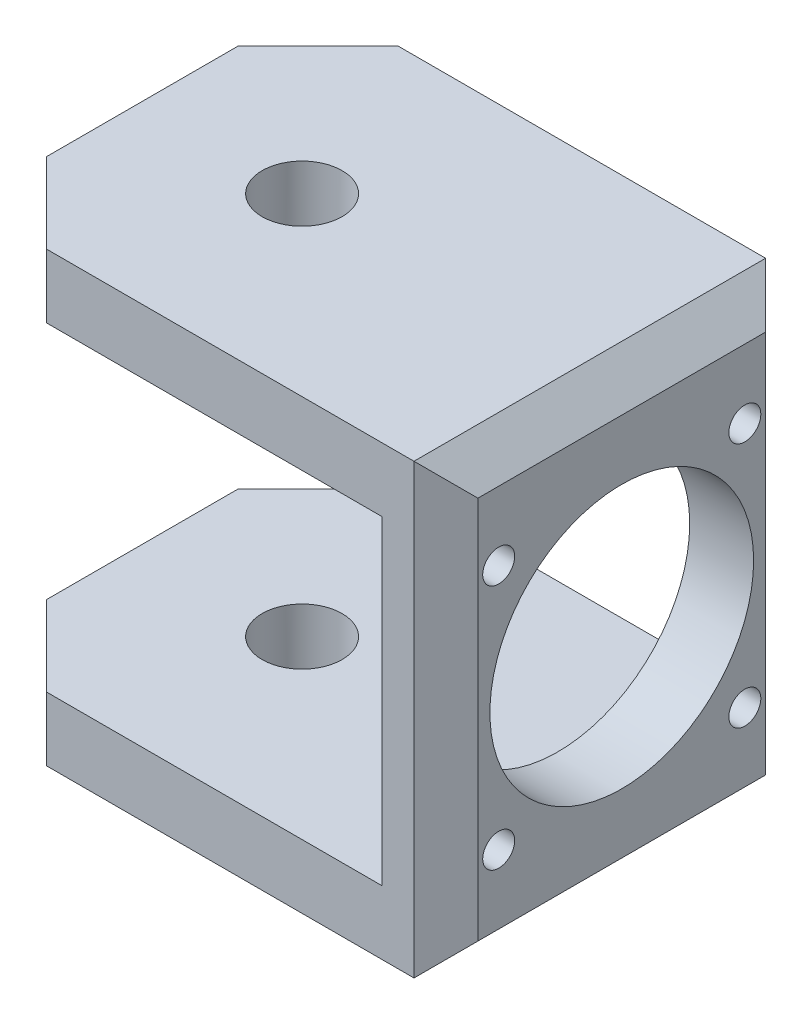
SolidWorks part; units mm, degrees
material "PLA Generic"
ref_plane "Front Plane" through (0, 0, 0) normal (0, 0, 1) x (1, 0, 0)
ref_plane "Top Plane" through (0, 0, 0) normal (0, 1, 0) x (1, 0, 0)
ref_plane "Right Plane" through (0, 0, 0) normal (1, 0, 0) x (0, 0, -1)
sketch "Sketch1" plane through (0, 0, 0) normal (0, 1, 0) x (1, 0, 0)
  line L1 (-15, -11) -> (15, -11)
  line L2 (-15, -11) -> (-15, 11)
  line L3 (-15, 11) -> (15, 11)
  line L4 (15, -11) -> (15, 11)
  line L5 (-15, -11) -> (15, 11) construction
  line L6 (-15, 11) -> (15, -11) construction
  point P0 (0, 0)
  dimension "D1" = 22
  dimension "D2" = 30
extrude "Boss-Extrude1" add sketch "Sketch1" along normal blind 4
sketch "Sketch2" plane through (0, 4, 0) normal (0, 1, 0) x (1, 0, 0)
  line L0 (-15, -11) -> (15, -11) construction
  line L1 (15, 11) -> (11, 11)
  line L2 (15, 11) -> (15, -11)
  line L3 (15, -11) -> (11, -11)
  line L4 (11, 11) -> (11, -11)
  dimension "D1" = 4
extrude "Boss-Extrude2" add sketch "Sketch2" along normal blind 20
sketch "Sketch3" plane through (0, 24, 0) normal (0, 1, 0) x (1, 0, 0)
  line L1 (15, 11) -> (-15, 11)
  line L2 (15, 11) -> (15, -11)
  line L3 (15, -11) -> (-15, -11)
  line L4 (-15, 11) -> (-15, -11)
extrude "Boss-Extrude3" add sketch "Sketch3" along normal blind 4
chamfer "Chamfer1" distance 5 angle 45 4 edges at (-15, 2, 11) (-15, 2, -11) (-15, 26, -11) (-15, 26, 11)
sketch "Sketch4" plane through (15, 0, 0) normal (1, 0, 0) x (0, 0, -1)
  circle A0 centre (0, 14) radius 8.25
  dimension "D1" = 16.5
extrude "Cut-Extrude1" cut sketch "Sketch4" against normal through all
ref_axis "Axis1" through (11, 14, 0) along (1, 0, 0)
sketch "Sketch5" plane through (15, 0, 0) normal (1, 0, 0) x (0, 0, -1)
  line L0 (0, 6.3) -> (-7.7, 6.3) construction
  line L1 (-7.7, 6.3) -> (0, 14) construction
  line L2 (0, 14) -> (0, 6.3) construction
  circle A0 centre (-7.7, 6.3) radius 1
  circle A1 centre (-7.7, 21.7) radius 1
  circle A2 centre (7.7, 21.7) radius 1
  circle A3 centre (7.7, 6.3) radius 1
  point P15 (0, 14)
  dimension "D3" = 2
  dimension "D1" = 45
  dimension "D2" = 7.7
  dimension "D4" = 4
extrude "Cut-Extrude2" cut sketch "Sketch5" against normal through all
chamfer "Chamfer2" distance 2 angle 45 4 edges at (15, 14, -11) (15, 0, 0) (15, 14, 11) (15, 28, 0)
sketch "Sketch6" plane through (0, 28, 0) normal (0, 1, 0) x (1, 0, 0)
  line L0 (11.1707, 0) -> (-17.3457, 0) construction
  line L1 (11, 0) -> (15, 0) construction
  line L2 (-15, 6) -> (-15, -6) construction
  circle A0 centre (-5, 0) radius 2.5
  dimension "D2" = 5
  dimension "D1" = 10
extrude "Cut-Extrude3" cut sketch "Sketch6" against normal through all
ref_plane "Plane1" through (23.2, 0, 0) normal (1, 0, 0) x (0, 0, -1)
sketch "Sketch7" plane through (23.2, 0, 0) normal (1, 0, 0) x (0, 0, -1)
  point P0 (0, 14)
